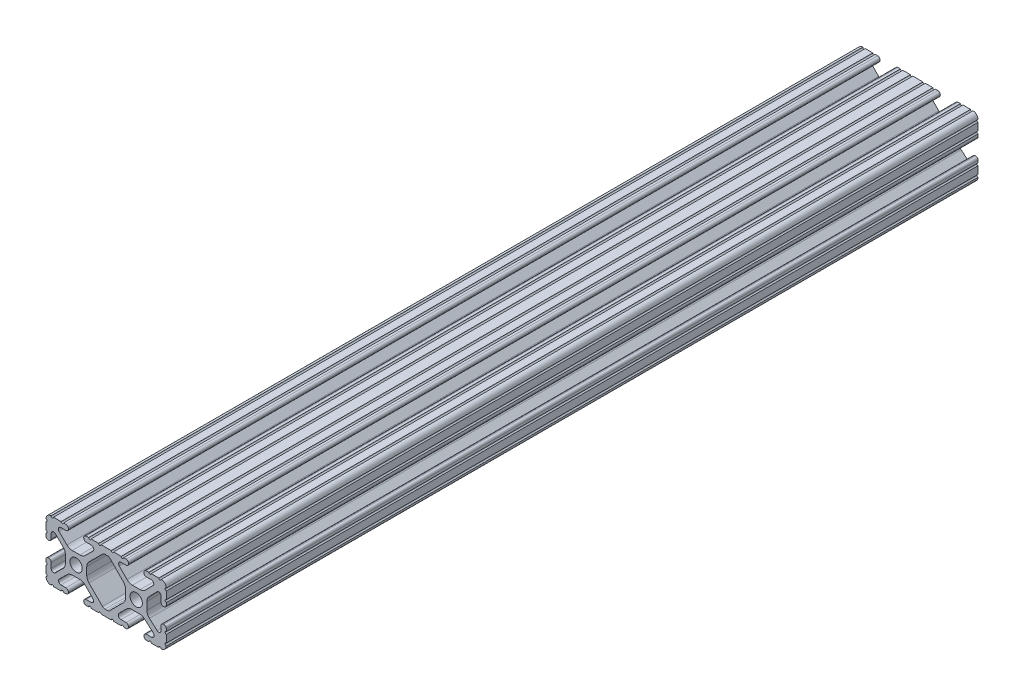
SolidWorks part; units mm, degrees
ref_plane "Front Plane" through (0, 0, 0) normal (0, 0, 1) x (1, 0, 0)
ref_plane "Top Plane" through (0, 0, 0) normal (0, 1, 0) x (1, 0, 0)
ref_plane "Right Plane" through (0, 0, 0) normal (1, 0, 0) x (0, 0, -1)
sketch "Sketch1" plane through (0, 0, 0) normal (0, 0, 1) x (1, 0, 0)
  line L0 (-7.2595, -3.8694) -> (-1.5457, -9.5728)
  line L1 (-8.1915, 1.6223) -> (-8.1915, -1.6223)
  line L2 (-1.504, 9.5765) -> (-7.252, 3.8768)
  line L3 (0.5515, 10.033) -> (-0.3952, 10.033)
  line L4 (7.2829, 3.8459) -> (1.6756, 9.5611)
  line L5 (8.1915, -1.6223) -> (8.1915, 1.6223)
  line L6 (1.5457, -9.5728) -> (7.2595, -3.8694)
  line L7 (-0.4332, -10.033) -> (0.4332, -10.033)
  line L8 (18.0171, 12.7) -> (16.9875, 12.7)
  line L9 (15.9385, 11.651) -> (15.9385, 11.5392)
  line L10 (16.9875, 10.4902) -> (19.1164, 10.4902)
  line L11 (19.8441, 8.7652) -> (16.619, 5.4551)
  line L12 (14.3449, 4.4958) -> (11.0833, 4.4958)
  line L13 (8.817, 5.4472) -> (5.5642, 8.7627)
  line L14 (6.2894, 10.4902) -> (8.4125, 10.4902)
  line L15 (9.4615, 11.5392) -> (9.4615, 11.651)
  line L16 (8.4125, 12.7) -> (7.3829, 12.7)
  line L17 (6.3669, 12.7) -> (3.1496, 12.7)
  line L18 (2.1336, 12.7) -> (-2.1336, 12.7)
  line L19 (-3.1496, 12.7) -> (-6.3669, 12.7)
  line L20 (-7.3829, 12.7) -> (-8.4125, 12.7)
  line L21 (-9.4615, 11.651) -> (-9.4615, 11.5392)
  line L22 (-8.4125, 10.4902) -> (-6.2836, 10.4902)
  line L23 (-5.5326, 8.6661) -> (-8.81, 5.4163)
  line L24 (-11.0455, 4.4958) -> (-14.3545, 4.4958)
  line L25 (-16.59, 5.4163) -> (-19.8674, 8.6661)
  line L26 (-19.1164, 10.4902) -> (-16.9875, 10.4902)
  line L27 (-15.9385, 11.5392) -> (-15.9385, 11.651)
  line L28 (-16.9875, 12.7) -> (-18.0171, 12.7)
  line L29 (-19.0331, 12.7) -> (-22.2504, 12.7)
  line L30 (-25.4, 9.5504) -> (-25.4, 6.3331)
  line L31 (-25.4, 5.3171) -> (-25.4, 4.2375)
  line L32 (-24.401, 3.2385) -> (-24.2392, 3.2385)
  line L33 (-23.1902, 4.2875) -> (-23.1902, 6.3347)
  line L34 (-21.434, 7.0665) -> (-18.148, 3.8082)
  line L35 (-17.2085, 1.5536) -> (-17.2085, -1.6952)
  line L36 (-18.1405, -3.9423) -> (-21.4316, -7.2274)
  line L37 (-23.1902, -6.498) -> (-23.1902, -4.2875)
  line L38 (-24.2392, -3.2385) -> (-24.351, -3.2385)
  line L39 (-25.4, -4.2875) -> (-25.4, -5.3171)
  line L40 (-25.4, -6.3331) -> (-25.4, -9.5504)
  line L41 (-22.2504, -12.7) -> (-19.0331, -12.7)
  line L42 (-18.0171, -12.7) -> (-16.9875, -12.7)
  line L43 (-15.9384, -11.651) -> (-15.9384, -11.5392)
  line L44 (-16.9875, -10.4902) -> (-19.1164, -10.4902)
  line L45 (-19.8341, -8.7551) -> (-16.4966, -5.4237)
  line L46 (-14.2536, -4.4958) -> (-11.1464, -4.4958)
  line L47 (-8.9034, -5.4237) -> (-5.5659, -8.7551)
  line L48 (-6.2836, -10.4902) -> (-8.4125, -10.4902)
  line L49 (-9.4616, -11.5392) -> (-9.4616, -11.651)
  line L50 (-8.4125, -12.7) -> (-7.3829, -12.7)
  line L51 (-6.3669, -12.7) -> (-3.1496, -12.7)
  line L52 (-2.1336, -12.7) -> (2.1336, -12.7)
  line L53 (3.1496, -12.7) -> (6.3669, -12.7)
  line L54 (7.3829, -12.7) -> (8.4125, -12.7)
  line L55 (9.4616, -11.651) -> (9.4616, -11.5392)
  line L56 (8.4125, -10.4902) -> (6.2894, -10.4902)
  line L57 (5.4807, -8.5353) -> (8.5979, -5.4237)
  line L58 (10.8409, -4.4958) -> (14.1026, -4.4958)
  line L59 (16.1879, -5.2766) -> (19.8682, -8.4822)
  line L60 (19.1164, -10.4902) -> (16.9875, -10.4902)
  line L61 (15.9384, -11.5392) -> (15.9384, -11.651)
  line L62 (16.9875, -12.7) -> (18.0171, -12.7)
  line L63 (19.0331, -12.7) -> (22.2504, -12.7)
  line L64 (25.4, -9.5504) -> (25.4, -6.3331)
  line L65 (25.4, -5.3171) -> (25.4, -4.2375)
  line L66 (24.401, -3.2385) -> (24.1892, -3.2385)
  line L67 (23.1902, -4.2375) -> (23.1902, -6.1559)
  line L68 (21.584, -6.8869) -> (18.2982, -4.025)
  line L69 (17.2085, -1.6308) -> (17.2085, 1.6308)
  line L70 (18.1094, 3.8465) -> (21.5263, 7.3534)
  line L71 (23.1902, 6.6769) -> (23.1902, 4.2375)
  line L72 (24.1892, 3.2385) -> (24.401, 3.2385)
  line L73 (25.4, 4.2375) -> (25.4, 5.3171)
  line L74 (25.4, 6.3332) -> (25.4, 9.5504)
  line L75 (22.2504, 12.7) -> (19.0331, 12.7)
  circle A0 centre (-12.7, 0) radius 2.6035
  circle A1 centre (12.7, 0) radius 2.6035
  arc A2 (-1.5457, -9.5728) -> (-0.4332, -10.033) centre (-0.4332, -8.4582) ccw
  arc A3 (-8.1915, -1.6223) -> (-7.2595, -3.8694) centre (-5.0165, -1.6223) ccw
  arc A4 (-7.252, 3.8768) -> (-8.1915, 1.6223) centre (-5.0165, 1.6223) ccw
  arc A5 (-0.3952, 10.033) -> (-1.504, 9.5765) centre (-0.3952, 8.4582) ccw
  arc A6 (1.6756, 9.5611) -> (0.5515, 10.033) centre (0.5515, 8.4582) ccw
  arc A7 (8.1915, 1.6223) -> (7.2829, 3.8459) centre (5.0165, 1.6223) ccw
  arc A8 (7.2595, -3.8694) -> (8.1915, -1.6223) centre (5.0165, -1.6223) ccw
  arc A9 (0.4332, -10.033) -> (1.5457, -9.5728) centre (0.4332, -8.4582) ccw
  arc A10 (18.0171, 12.7) -> (19.0331, 12.7) centre (18.5251, 12.7) ccw
  arc A11 (16.9875, 12.7) -> (15.9385, 11.651) centre (16.9875, 11.651) ccw
  arc A12 (15.9385, 11.5392) -> (16.9875, 10.4902) centre (16.9875, 11.5392) ccw
  arc A13 (19.8441, 8.7652) -> (19.1164, 10.4902) centre (19.1164, 9.4742) ccw
  arc A14 (14.3449, 4.4958) -> (16.619, 5.4551) centre (14.3449, 7.6708) ccw
  arc A15 (8.817, 5.4472) -> (11.0833, 4.4958) centre (11.0833, 7.6708) ccw
  arc A16 (6.2894, 10.4902) -> (5.5642, 8.7627) centre (6.2894, 9.4742) ccw
  arc A17 (8.4125, 10.4902) -> (9.4615, 11.5392) centre (8.4125, 11.5392) ccw
  arc A18 (9.4615, 11.651) -> (8.4125, 12.7) centre (8.4125, 11.651) ccw
  arc A19 (6.3669, 12.7) -> (7.3829, 12.7) centre (6.8749, 12.7) ccw
  arc A20 (2.1336, 12.7) -> (3.1496, 12.7) centre (2.6416, 12.7) ccw
  arc A21 (-3.1496, 12.7) -> (-2.1336, 12.7) centre (-2.6416, 12.7) ccw
  arc A22 (-7.3829, 12.7) -> (-6.3669, 12.7) centre (-6.8749, 12.7) ccw
  arc A23 (-8.4125, 12.7) -> (-9.4615, 11.651) centre (-8.4125, 11.651) ccw
  arc A24 (-9.4615, 11.5392) -> (-8.4125, 10.4902) centre (-8.4125, 11.5392) ccw
  arc A25 (-5.5326, 8.6661) -> (-6.2836, 10.4902) centre (-6.2836, 9.4235) ccw
  arc A26 (-11.0455, 4.4958) -> (-8.81, 5.4163) centre (-11.0455, 7.6708) ccw
  arc A27 (-16.59, 5.4163) -> (-14.3545, 4.4958) centre (-14.3545, 7.6708) ccw
  arc A28 (-19.1164, 10.4902) -> (-19.8674, 8.6661) centre (-19.1164, 9.4235) ccw
  arc A29 (-16.9875, 10.4902) -> (-15.9385, 11.5392) centre (-16.9875, 11.5392) ccw
  arc A30 (-15.9385, 11.651) -> (-16.9875, 12.7) centre (-16.9875, 11.651) ccw
  arc A31 (-19.0331, 12.7) -> (-18.0171, 12.7) centre (-18.5251, 12.7) ccw
  arc A32 (-23.2664, 12.6998) -> (-22.2504, 12.7) centre (-22.7584, 12.7) ccw
  arc A33 (-23.2664, 12.6998) -> (-25.3998, 10.5664) centre (-23.2918, 10.5918) ccw
  arc A34 (-25.4, 9.5504) -> (-25.3998, 10.5664) centre (-25.4, 10.0584) ccw
  arc A35 (-25.4, 5.3171) -> (-25.4, 6.3331) centre (-25.4, 5.8251) ccw
  arc A36 (-25.4, 4.2375) -> (-24.401, 3.2385) centre (-24.401, 4.2375) ccw
  arc A37 (-24.2392, 3.2385) -> (-23.1902, 4.2875) centre (-24.2392, 4.2875) ccw
  arc A38 (-21.434, 7.0665) -> (-23.1902, 6.3347) centre (-22.1596, 6.3347) ccw
  arc A39 (-17.2085, 1.5536) -> (-18.148, 3.8082) centre (-20.3835, 1.5536) ccw
  arc A40 (-18.1405, -3.9423) -> (-17.2085, -1.6952) centre (-20.3835, -1.6952) ccw
  arc A41 (-23.1902, -6.498) -> (-21.4316, -7.2274) centre (-22.1596, -6.498) ccw
  arc A42 (-23.1902, -4.2875) -> (-24.2392, -3.2385) centre (-24.2392, -4.2875) ccw
  arc A43 (-24.351, -3.2385) -> (-25.4, -4.2875) centre (-24.351, -4.2875) ccw
  arc A44 (-25.4, -6.3331) -> (-25.4, -5.3171) centre (-25.4, -5.8251) ccw
  arc A45 (-25.3998, -10.5664) -> (-25.4, -9.5504) centre (-25.4, -10.0584) ccw
  arc A46 (-25.3998, -10.5664) -> (-23.2664, -12.6998) centre (-23.2918, -10.5918) ccw
  arc A47 (-22.2504, -12.7) -> (-23.2664, -12.6998) centre (-22.7584, -12.7) ccw
  arc A48 (-18.0171, -12.7) -> (-19.0331, -12.7) centre (-18.5251, -12.7) ccw
  arc A49 (-16.9875, -12.7) -> (-15.9384, -11.651) centre (-16.9875, -11.651) ccw
  arc A50 (-15.9384, -11.5392) -> (-16.9875, -10.4902) centre (-16.9875, -11.5392) ccw
  arc A51 (-19.8341, -8.7551) -> (-19.1164, -10.4902) centre (-19.1164, -9.4742) ccw
  arc A52 (-14.2536, -4.4958) -> (-16.4966, -5.4237) centre (-14.2536, -7.6708) ccw
  arc A53 (-8.9034, -5.4237) -> (-11.1464, -4.4958) centre (-11.1464, -7.6708) ccw
  arc A54 (-6.2836, -10.4902) -> (-5.5659, -8.7551) centre (-6.2836, -9.4742) ccw
  arc A55 (-8.4125, -10.4902) -> (-9.4616, -11.5392) centre (-8.4125, -11.5392) ccw
  arc A56 (-9.4616, -11.651) -> (-8.4125, -12.7) centre (-8.4125, -11.651) ccw
  arc A57 (-6.3669, -12.7) -> (-7.3829, -12.7) centre (-6.8749, -12.7) ccw
  arc A58 (-2.1336, -12.7) -> (-3.1496, -12.7) centre (-2.6416, -12.7) ccw
  arc A59 (3.1496, -12.7) -> (2.1336, -12.7) centre (2.6416, -12.7) ccw
  arc A60 (7.3829, -12.7) -> (6.3669, -12.7) centre (6.8749, -12.7) ccw
  arc A61 (8.4125, -12.7) -> (9.4616, -11.651) centre (8.4125, -11.651) ccw
  arc A62 (9.4616, -11.5392) -> (8.4125, -10.4902) centre (8.4125, -11.5392) ccw
  arc A63 (5.4807, -8.5353) -> (6.2894, -10.4902) centre (6.2894, -9.3455) ccw
  arc A64 (10.8409, -4.4958) -> (8.5979, -5.4237) centre (10.8409, -7.6708) ccw
  arc A65 (16.1879, -5.2766) -> (14.1026, -4.4958) centre (14.1026, -7.6708) ccw
  arc A66 (19.1164, -10.4902) -> (19.8682, -8.4822) centre (19.1164, -9.3455) ccw
  arc A67 (16.9875, -10.4902) -> (15.9384, -11.5392) centre (16.9875, -11.5392) ccw
  arc A68 (15.9384, -11.651) -> (16.9875, -12.7) centre (16.9875, -11.651) ccw
  arc A69 (19.0331, -12.7) -> (18.0171, -12.7) centre (18.5251, -12.7) ccw
  arc A70 (23.2664, -12.6998) -> (22.2504, -12.7) centre (22.7584, -12.7) ccw
  arc A71 (23.2664, -12.6998) -> (25.3998, -10.5664) centre (23.2918, -10.5918) ccw
  arc A72 (25.4, -9.5504) -> (25.3998, -10.5664) centre (25.4, -10.0584) ccw
  arc A73 (25.4, -5.3171) -> (25.4, -6.3331) centre (25.4, -5.8251) ccw
  arc A74 (25.4, -4.2375) -> (24.401, -3.2385) centre (24.401, -4.2375) ccw
  arc A75 (24.1892, -3.2385) -> (23.1902, -4.2375) centre (24.1892, -4.2375) ccw
  arc A76 (21.584, -6.8869) -> (23.1902, -6.1559) centre (22.2207, -6.1559) ccw
  arc A77 (17.2085, -1.6308) -> (18.2982, -4.025) centre (20.3835, -1.6308) ccw
  arc A78 (18.1094, 3.8465) -> (17.2085, 1.6308) centre (20.3835, 1.6308) ccw
  arc A79 (23.1902, 6.6769) -> (21.5263, 7.3534) centre (22.2207, 6.6769) ccw
  arc A80 (23.1902, 4.2375) -> (24.1892, 3.2385) centre (24.1892, 4.2375) ccw
  arc A81 (24.401, 3.2385) -> (25.4, 4.2375) centre (24.401, 4.2375) ccw
  arc A82 (25.4, 6.3332) -> (25.4, 5.3171) centre (25.4, 5.8251) ccw
  arc A83 (25.3998, 10.5664) -> (25.4, 9.5504) centre (25.4, 10.0584) ccw
  arc A84 (25.3998, 10.5664) -> (23.2664, 12.6998) centre (23.2918, 10.5918) ccw
  arc A85 (22.2504, 12.7) -> (23.2664, 12.6998) centre (22.7584, 12.7) ccw
  point P248 (0, 10.033)
extrude "Boss-Extrude1" add sketch "Sketch1" along normal mid plane 342.9
ref_plane "Plane1" through (0, 0, 0) normal (0, -1, 0) x (-1, 0, 0)
ref_axis "Axis1" through (12.7, 0, 171.45) along (0, 0, -1)
ref_plane "Plane2" through (12.7, 0, 0) normal (-1, 0, 0) x (0, 0, -1)
